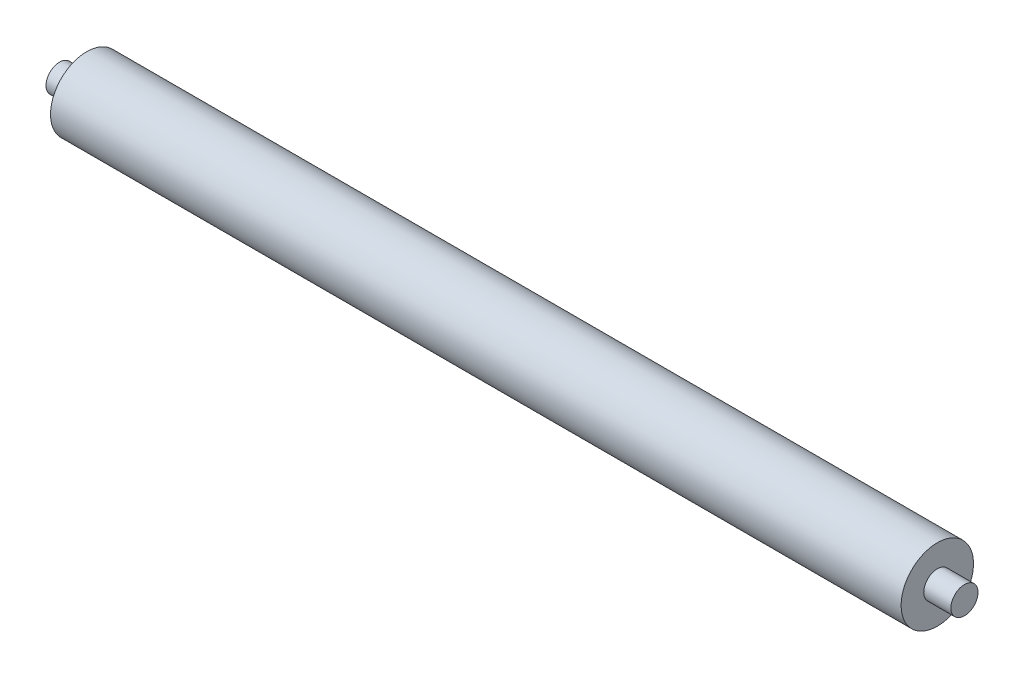
SolidWorks part; units mm, degrees
ref_plane "Plan de face" through (0, 0, 0) normal (0, 0, 1) x (1, 0, 0)
ref_plane "Plan de dessus" through (0, 0, 0) normal (0, 1, 0) x (1, 0, 0)
ref_plane "Plan de droite" through (0, 0, 0) normal (1, 0, 0) x (0, 0, -1)
sketch "Esquisse1" plane through (0, 0, 0) normal (0, 0, 1) x (1, 0, 0)
  line L0 (0, 0) -> (100, 0)
  line L1 (100, 0) -> (100, 1.5)
  line L2 (100, 1.5) -> (97, 1.5)
  line L3 (97, 1.5) -> (97, 4)
  line L4 (97, 4) -> (3, 4)
  line L5 (3, 4) -> (3, 1.5)
  line L6 (3, 1.5) -> (0, 1.5)
  line L7 (0, 1.5) -> (0, 0)
  dimension "D1" = 1.5
  dimension "D2" = 4
  dimension "D3" = 3
  dimension "D4" = 100
revolve "Révolution1" add sketch "Esquisse1" angle 360 about L0
